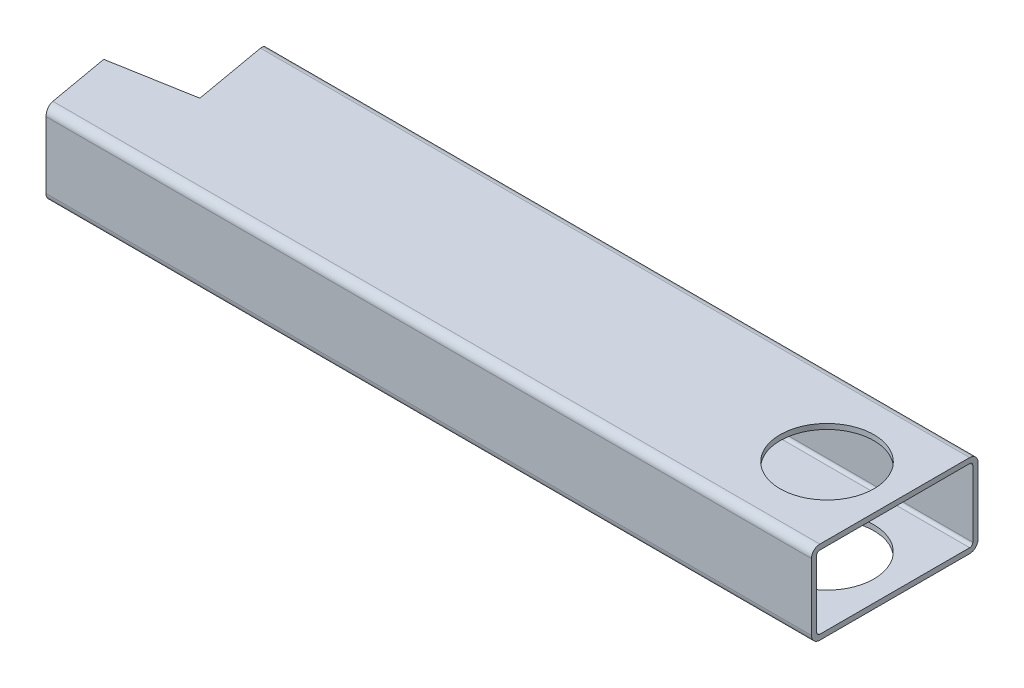
SolidWorks part; units mm, degrees
material "6061 Alloy"
ref_plane "Front" through (0, 0, 0) normal (0, 0, 1) x (1, 0, 0)
ref_plane "Top" through (0, 0, 0) normal (0, 1, 0) x (1, 0, 0)
ref_plane "Right" through (0, 0, 0) normal (1, 0, 0) x (0, 0, -1)
sketch "Sketch1" plane through (0, 0, 0) normal (1, 0, 0) x (0, 0, -1)
  line L1 (-2.54, 0) -> (-48.26, 0)
  line L2 (0, 2.54) -> (0, 22.86)
  line L3 (-2.54, 25.4) -> (-48.26, 25.4)
  line L4 (-50.8, 2.54) -> (-50.8, 22.86)
  arc A0 (-50.8, 2.54) -> (-48.26, 0) centre (-48.26, 2.54) ccw
  arc A1 (-2.54, 0) -> (0, 2.54) centre (-2.54, 2.54) ccw
  arc A2 (0, 22.86) -> (-2.54, 25.4) centre (-2.54, 22.86) ccw
  arc A3 (-48.26, 25.4) -> (-50.8, 22.86) centre (-48.26, 22.86) ccw
  point P7 (-50.8, 0)
  point P10 (0, 0)
  point P13 (0, 25.4)
  dimension "D3" = 2.54
  dimension "D1" = 25.4
  dimension "D2" = 50.8
extrude "Extrude-Thin1" add sketch "Sketch1" against normal blind 243.6368 thin thin type one direction reverse wall 1.5875
sketch "Sketch3" plane through (0, 25.4, 0) normal (0, 1, 0) x (1, 0, 0)
  line L0 (0, 49.2125) -> (79.6022, 243.0747)
  line L1 (0, -1.5875) -> (25.4, -1.5875)
  line L2 (0, -1.5875) -> (0, 49.2125)
  line L3 (0, 49.2125) -> (25.4, 49.2125)
  line L4 (25.4, -1.5875) -> (25.4, 49.2125)
  line L5 (79.6022, 243.0747) -> (126.5949, 223.7789)
  line L6 (126.5949, 223.7789) -> (34.0567, -1.5875)
  line L7 (71.7537, 223.9604) -> (118.7463, 204.6646) construction
  line L8 (95.25, 214.3125) -> (0, 214.3125)
  line L9 (0, 49.2125) -> (0, 289.0515)
  line L10 (25.4, -1.5875) -> (34.0567, -1.5875)
  circle A0 centre (95.25, 214.3125) radius 14.3129
  point P11 (95.25, 214.3125)
  dimension "D4" = 28.6258
  dimension "D5" = 6.35
  dimension "D1" = 25.4
  dimension "D2" = 50.8
  dimension "D3" = 50.8
  dimension "D6" = 95.25
  dimension "D7" = 165.1
  dimension "D8" = 243.6254
  dimension "D9" = 209.5687
sketch "Sketch4" plane through (0, 25.4, 0) normal (0, 1, 0) x (1, 0, 0)
  line L0 (-20.6629, -48.26) -> (-20.6629, -2.54) construction
  line L2 (-243.6368, -2.54) -> (0, -2.54) construction
  line L3 (-243.6368, -48.26) -> (0, -48.26) construction
  line L4 (0, -2.54) -> (0, -48.26) construction
  line L5 (0, 0) -> (-216.7798, 0) construction
  line L6 (-243.6368, 0) -> (0, 0) construction
  line L7 (-216.7798, 0) -> (-212.3692, -25.0141)
  line L8 (-212.3692, -25.0141) -> (-237.2868, -29.4078)
  line L9 (-237.2868, -29.4078) -> (-233.5148, -50.8)
  line L10 (-243.6368, -50.8) -> (0, -50.8) construction
  line L11 (-216.7798, 0) -> (-243.6368, 0)
  line L12 (-243.6368, 0) -> (-243.6368, -30.5274)
  line L13 (-233.5148, -50.8) -> (-243.6368, -50.8)
  line L14 (-243.6368, -50.8) -> (-243.6368, -30.5274)
  line L15 (-243.6368, -30.5274) -> (-212.3692, -25.0141) construction
  circle A0 centre (-20.6629, -25.4) radius 14.3129
  point P5 (-20.6629, -25.4)
  point P22 (-243.6368, -34.5021)
  dimension "D1" = 28.6258
  dimension "D2" = 6.35
  dimension "D3" = 25.4
  dimension "D4" = 31.75
  dimension "D5" = 80
  dimension "D6" = 6.35
extrude "Cut-Extrude1" cut sketch "Sketch4" against normal through all and the other way through all
